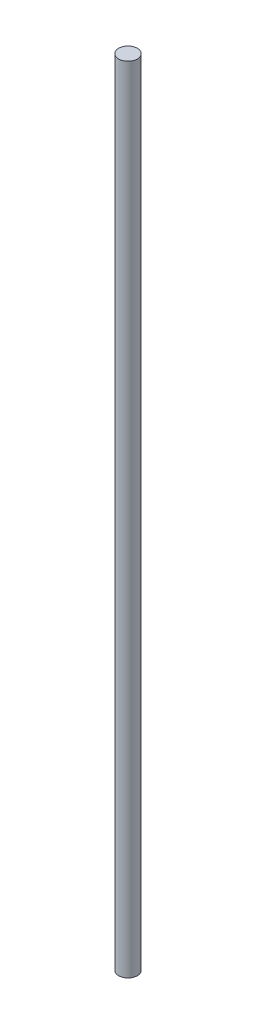
SolidWorks part; units mm, degrees
material "AISI 1020"
ref_plane "Front Plane" through (0, 0, 0) normal (0, 0, 1) x (1, 0, 0)
ref_plane "Top Plane" through (0, 0, 0) normal (0, 1, 0) x (1, 0, 0)
ref_plane "Right Plane" through (0, 0, 0) normal (1, 0, 0) x (0, 0, -1)
sketch "Sketch1" plane through (0, 0, 0) normal (0, 1, 0) x (1, 0, 0)
  circle A0 centre (0, 0) radius 4
  dimension "D1" = 8
extrude "Boss-Extrude1" add sketch "Sketch1" along normal blind 170 and the other way blind 170
cosmetic thread "Cosmetic Thread1"
